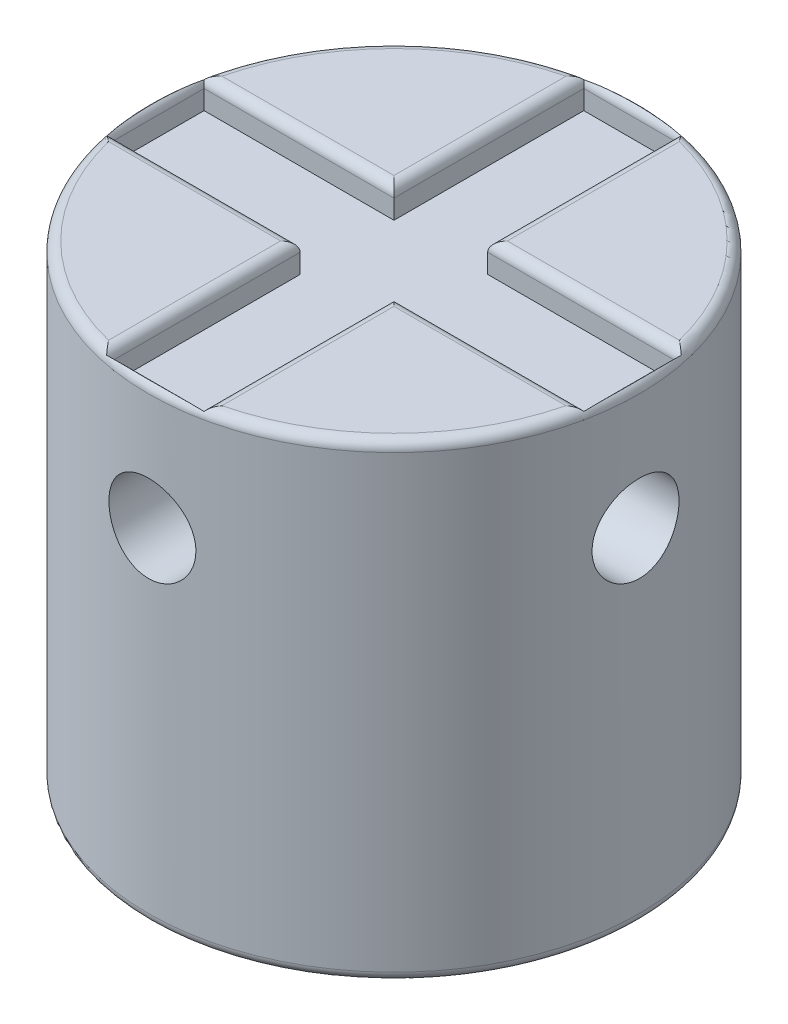
SolidWorks part; units mm, degrees
ref_plane "Front Plane" through (0, 0, 0) normal (0, 0, 1) x (1, 0, 0)
ref_plane "Top Plane" through (0, 0, 0) normal (0, 1, 0) x (1, 0, 0)
ref_plane "Right Plane" through (0, 0, 0) normal (1, 0, 0) x (0, 0, -1)
sketch "Sketch1" plane through (0, 0, 0) normal (0, 1, 0) x (1, 0, 0)
  circle A0 centre (0, 0) radius 12.7
  dimension "D1" = 25.4
extrude "Boss-Extrude1" add sketch "Sketch1" along normal blind 24.3
sketch "Sketch3" plane through (0, 0, 0) normal (0, 0, 1) x (1, 0, 0)
  line L0 (12.7, 24.3) -> (-12.7, 24.3) construction
  circle A0 centre (0, 17.77) radius 2.25
  dimension "D1" = 4.5
  dimension "D2" = 6.53
extrude "Cut-Extrude1" cut sketch "Sketch3" against normal through all both and the other way through all
sketch "Sketch4" plane through (0, 0, 0) normal (1, 0, 0) x (0, 0, -1)
  line L0 (12.7, 24.3) -> (-12.7, 24.3) construction
  circle A0 centre (0, 17.77) radius 2.25
  dimension "D1" = 4.5
  dimension "D2" = 6.53
extrude "Cut-Extrude2" cut sketch "Sketch4" against normal through all both and the other way through all
sketch "Sketch6" plane through (0, 24.3, 0) normal (0, 1, 0) x (1, 0, 0)
  line L1 (-2.425, -12.25) -> (2.425, -12.25)
  line L2 (-2.425, -12.25) -> (-2.425, 12.25)
  line L3 (-2.425, 12.25) -> (2.425, 12.25)
  line L4 (2.425, -12.25) -> (2.425, 12.25)
  line L5 (-2.425, -12.25) -> (2.425, 12.25) construction
  line L6 (-2.425, 12.25) -> (2.425, -12.25) construction
  line L7 (-12.25, 2.425) -> (12.25, 2.425)
  line L8 (-12.25, 2.425) -> (-12.25, -2.425)
  line L9 (-12.25, -2.425) -> (12.25, -2.425)
  line L10 (12.25, 2.425) -> (12.25, -2.425)
  line L11 (-12.25, 2.425) -> (12.25, -2.425) construction
  line L12 (-12.25, -2.425) -> (12.25, 2.425) construction
  point P0 (0, 0)
  point P6 (0, 0)
  dimension "D1" = 4.85
  dimension "D2" = 4.85
  dimension "D3" = 24.5
  dimension "D4" = 24.5
extrude "Cut-Extrude4" cut sketch "Sketch6" against normal blind 1.5 contours L8 L9 L2 L7 | L2 L9 L4 L7 | L2 L7 L4 L3 | L10 L7 L4 L9 | L9 L2 L1 L4 region at (0, 24.3, 7.3375) region at (-7.3375, 24.3, 0) region at (0, 24.3, 0) region at (7.3375, 24.3, 0) region at (0, 24.3, -7.3375)
sketch "Sketch5" plane through (-21.8862, 0, 0) normal (0, 1, 0) x (-1, 0, 0)
  circle A0 centre (-21.8862, 0) radius 7.3152
  circle A1 centre (-21.8862, 0) radius 9.144
  dimension "D1" = 18.288
  dimension "D2" = 1.8288
extrude "Cut-Extrude3" cut sketch "Sketch5" along normal blind 2 from offset 0
fillet "Fillet1" radius 0.508 18 edges at (0, 0, 7.3152) (0, 0, 9.144) (0, 24.3, 12.7) (-7.3375, 24.3, 2.425) (-2.425, 24.3, 7.3375) (0, 24.3, 12.25) (2.425, 24.3, 7.3375) (7.3375, 24.3, 2.425) (12.25, 24.3, 0) (7.3375, 24.3, -2.425) (2.425, 24.3, -7.3375) (0, 24.3, -12.25) (-2.425, 24.3, -7.3375) (-7.3375, 24.3, -2.425) (-12.25, 24.3, 0) (0, 0, 12.7) (0, 2, 7.3152) (0, 2, 9.144)
equation "\"len\"=24.5"
equation "\"D3@Sketch6\"=\"len\""
equation "\"D4@Sketch6\"=\"len\""
equation "\"width\"=4.85"
equation "\"D1@Sketch6\"=\"width\""
equation "\"D2@Sketch6\"=\"width\""
